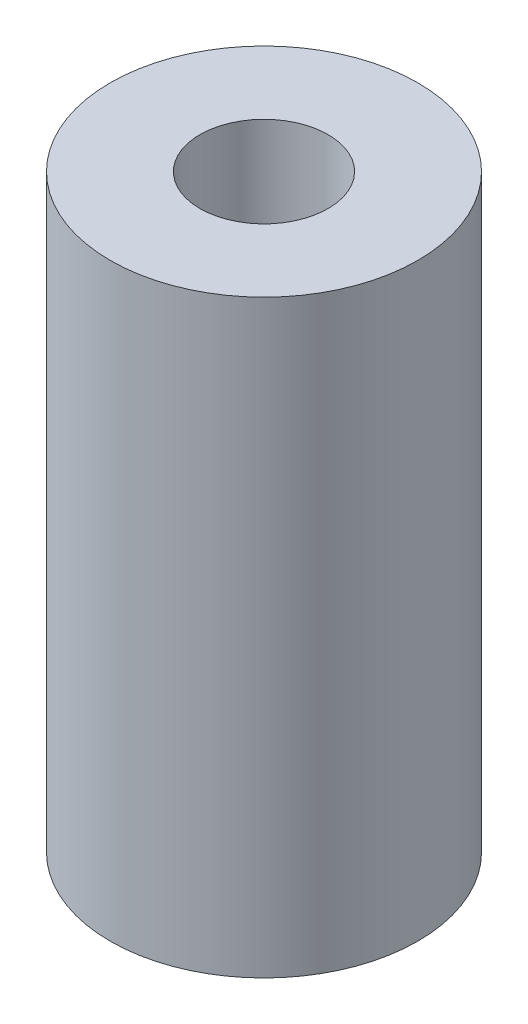
SolidWorks part; units mm, degrees
ref_plane "Front Plane" through (0, 0, 0) normal (0, 0, 1) x (1, 0, 0)
ref_plane "Top Plane" through (0, 0, 0) normal (0, 1, 0) x (1, 0, 0)
ref_plane "Right Plane" through (0, 0, 0) normal (1, 0, 0) x (0, 0, -1)
sketch "Sketch1" plane through (0, 0, 0) normal (0, 1, 0) x (1, 0, 0)
  circle A0 centre (0, 0) radius 6
  circle A1 centre (0, 0) radius 2.5
  dimension "D1" = 12
  dimension "D2" = 5
extrude "Boss-Extrude1" add sketch "Sketch1" along normal blind 23
